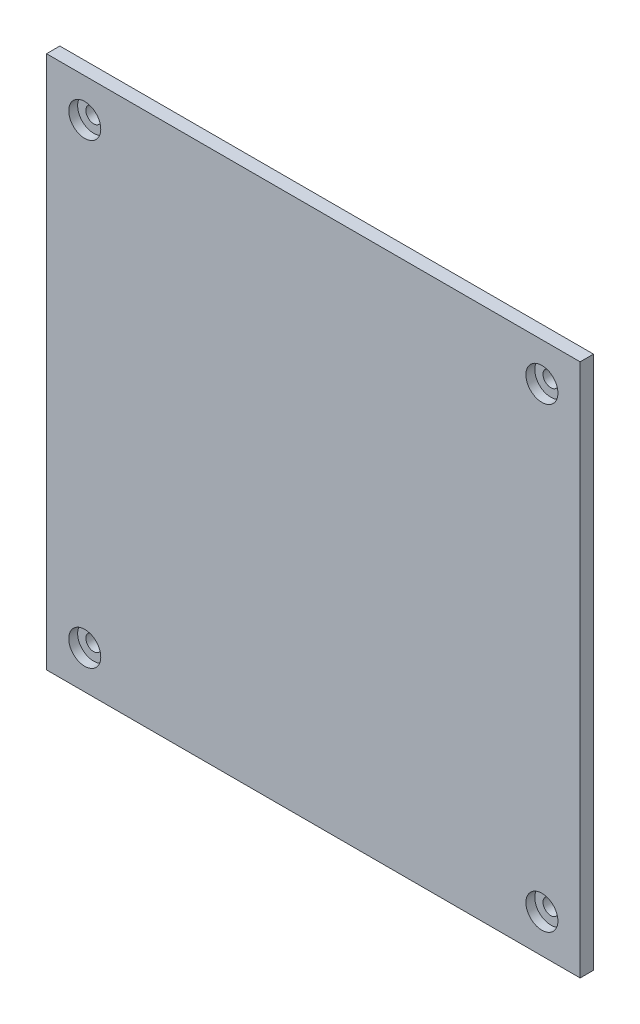
SolidWorks part; units mm, degrees
material "PVC 0.007 Plasticizado"
ref_plane "Plano frontal" through (0, 0, 0) normal (0, 0, 1) x (1, 0, 0)
ref_plane "Plano superior" through (0, 0, 0) normal (0, 1, 0) x (1, 0, 0)
ref_plane "Plano direito" through (0, 0, 0) normal (1, 0, 0) x (0, 0, -1)
sketch "Esboço1" plane through (0, 0, 0) normal (0, 0, 1) x (1, 0, 0)
  line L1 (-60, -60) -> (60, -60)
  line L2 (-60, -60) -> (-60, 60)
  line L3 (-60, 60) -> (60, 60)
  line L4 (60, -60) -> (60, 60)
  line L5 (-60, -60) -> (60, 60) construction
  line L6 (-60, 60) -> (60, -60) construction
  point P0 (0, 0)
  dimension "D1" = 120
  dimension "D2" = 120
extrude "Ressalto-extrusão1" add sketch "Esboço1" along normal blind 3
sketch "Esboço2" plane through (0, 0, 0) normal (0, 0, -1) x (-1, 0, 0)
  line L8 (-56.4, 56.4) -> (-56.4, -56.4)
  line L9 (-56.4, -56.4) -> (56.4, -56.4)
  line L10 (56.4, -56.4) -> (56.4, 56.4)
  line L11 (56.4, 56.4) -> (-56.4, 56.4)
  line L12 (-56.4, 56.4) -> (-56.4, -56.4)
  line L13 (-56.4, -56.4) -> (56.4, -56.4)
  line L14 (56.4, -56.4) -> (56.4, 56.4)
  line L15 (56.4, 56.4) -> (-56.4, 56.4)
  dimension "D1" = 3.6
extrude "Ressalto-extrusão2" add sketch "Esboço2" along normal blind 2
sketch "Esboço3" plane through (0, 0, -2) normal (0, 0, -1) x (-1, 0, 0)
  line L8 (54.4, 54.4) -> (-54.4, 54.4)
  line L9 (-54.4, 54.4) -> (-54.4, -54.4)
  line L10 (-54.4, -54.4) -> (54.4, -54.4)
  line L11 (54.4, -54.4) -> (54.4, 54.4)
  line L12 (54.4, 54.4) -> (-54.4, 54.4)
  line L13 (-54.4, 54.4) -> (-54.4, -54.4)
  line L14 (-54.4, -54.4) -> (54.4, -54.4)
  line L15 (54.4, -54.4) -> (54.4, 54.4)
  dimension "D1" = 2
extrude "Corte-extrusão1" cut sketch "Esboço3" against normal blind 2
sketch "Esboço5" plane through (0, 0, 0) normal (0, 0, -1) x (-1, 0, 0)
  line L0 (56.4, -56.4) -> (56.4, 56.4) construction
  line L1 (56.4, 56.4) -> (-56.4, 56.4) construction
  line L2 (60, 60) -> (60, -60) construction
  circle A0 centre (51.4, 51.4) radius 5
  dimension "D1" = 8.6
extrude "Ressalto-extrusão3" add sketch "Esboço5" along normal blind 2
mirror "Espelhar1" about plane through (0, 0, 0) normal (1, 0, 0) of "Ressalto-extrusão3"
mirror "Espelhar2" about plane through (0, 0, 0) normal (0, 1, 0) of "Espelhar1"
chamfer "Chanfro1" distance 0.5 angle 45 4 edges at (-56.4, 0, -2) (0, -56.4, -2) (56.4, 0, -2) (0, 56.4, -2)
fillet "Filete1" radius 2 8 edges at (0, -54.4, 0) (47.8645, -47.8645, 0) (54.4, 0, 0) (47.8645, 47.8645, 0) (0, 54.4, 0) (-47.8645, 47.8645, 0) (-54.4, 0, 0) (-47.8645, -47.8645, 0)
sketch "Esboço6" plane through (0, 0, 3) normal (0, 0, 1) x (1, 0, 0)
  line L0 (-60, 60) -> (-60, -60) construction
  line L1 (60, 60) -> (-60, 60) construction
  circle A0 centre (-51.4, 51.4) radius 3.6
  dimension "D1" = 8.6
  dimension "D3" = 7.2
  dimension "D2" = 8.6
extrude "Corte-extrusão2" cut sketch "Esboço6" against normal blind 2
sketch "Esboço7" plane through (0, 0, 1) normal (0, 0, 1) x (1, 0, 0)
  circle A0 centre (-51.4, 51.4) radius 1.75
  dimension "D1" = 3.5
extrude "Corte-extrusão3" cut sketch "Esboço7" against normal through all
mirror "Espelhar3" about plane through (0, 0, 0) normal (1, 0, 0) of "Corte-extrusão2", "Corte-extrusão3"
mirror "Espelhar4" about plane through (0, 0, 0) normal (0, 1, 0) of "Espelhar3"
